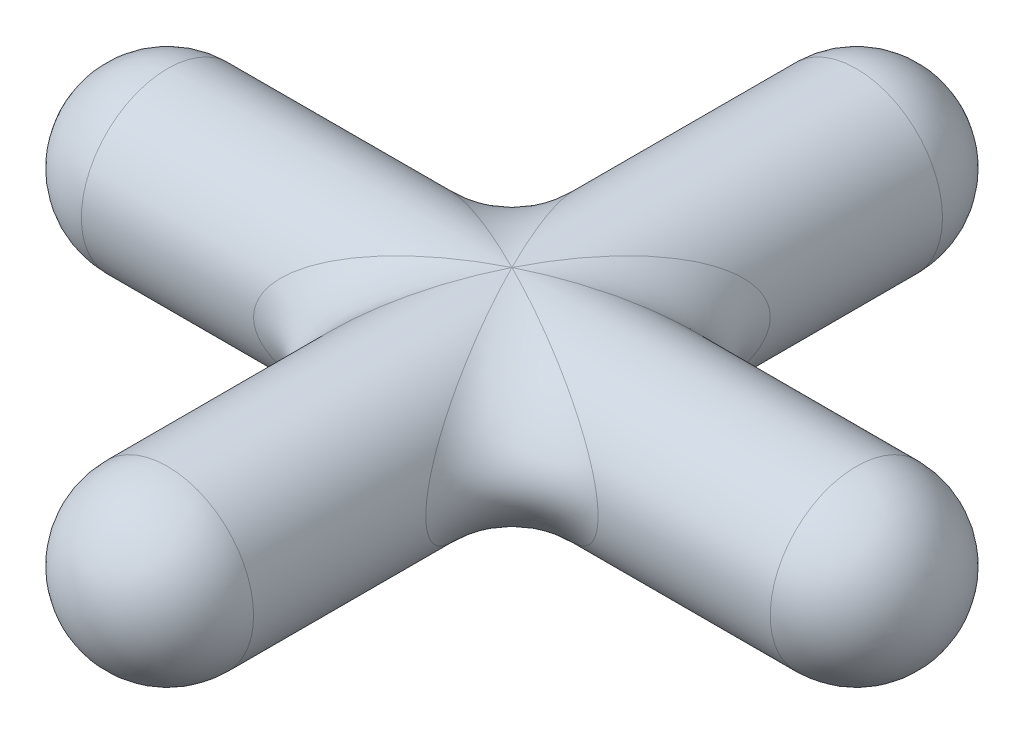
SolidWorks part; units mm, degrees
ref_plane "Front Plane" through (0, 0, 0) normal (0, 0, 1) x (1, 0, 0)
ref_plane "Top Plane" through (0, 0, 0) normal (0, 1, 0) x (1, 0, 0)
ref_plane "Right Plane" through (0, 0, 0) normal (1, 0, 0) x (0, 0, -1)
sketch "Sketch1" plane through (0, 0, 0) normal (1, 0, 0) x (0, 0, -1)
  circle A0 centre (0, 0) radius 2.5
  dimension "D1" = 5
extrude "Boss-Extrude1" add sketch "Sketch1" along normal blind 20 contours A0
sketch "Sketch2" plane through (0, 0, 0) normal (0, 0, 1) x (1, 0, 0)
  line L0 (0, 0) -> (20, 0) construction
  line L1 (20, -2.5) -> (20, 2.5) construction
  line L2 (10, 0) -> (10, 2.3665) construction
  point P6 (10, 0)
  point P8 (0, 0)
dome "Dome1" faces to dome 1 distance 2.5 reverse direction no elliptical dome no face at (20, 0, -2.5) parameters "D1"=2.5
dome "Dome2" faces to dome 1 distance 2.5 reverse direction no elliptical dome no face at (0, 0, -2.5) parameters "D1"=2.5
pattern_circular "CirPattern1" count 2 over 90 about axis through (10, 0, 0) along (0, 1, 0) of "Boss-Extrude1", "Dome1", "Dome2" reverse direction yes
fillet "Fillet1" radius 2.5 4 edges at (12.5, 0, 2.5) (7.5, 0, 2.5) (7.5, 0, -2.5) (12.5, 0, -2.5)
sketch "Sketch3" plane through (0, 0, 0) normal (0, 0, 1) x (1, 0, 0)
  line L0 (10, -2.5) -> (10, 2.5) construction
  circle A0 centre (10, 0) radius 2.5 construction
ref_plane "Plane1" through (10, 0, 0) normal (1, 0, 0) x (0, 0, -1)
